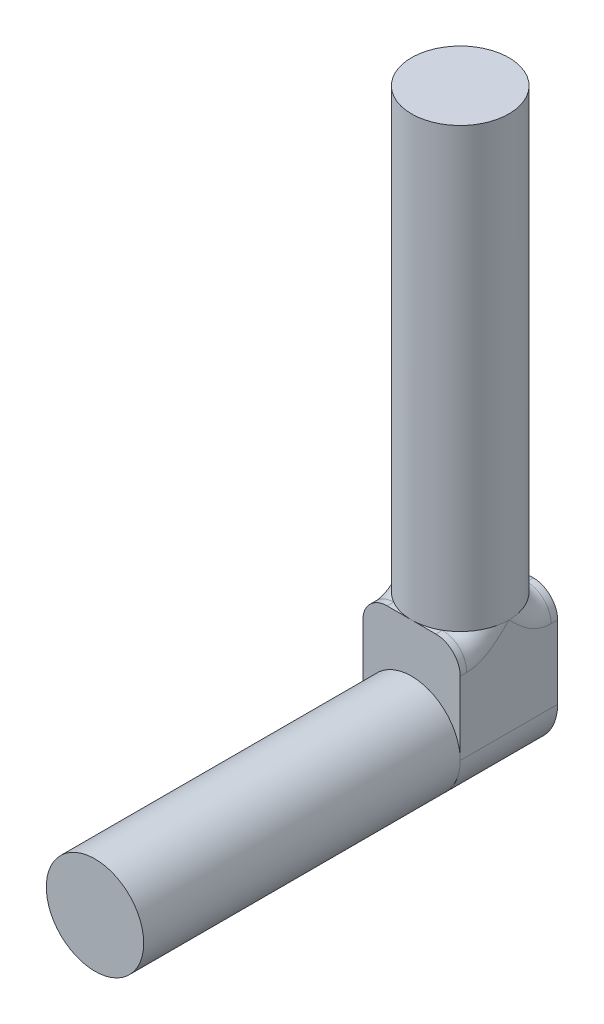
SolidWorks part; units mm, degrees
ref_plane "Front Plane" through (0, 0, 0) normal (0, 0, 1) x (1, 0, 0)
ref_plane "Top Plane" through (0, 0, 0) normal (0, 1, 0) x (1, 0, 0)
ref_plane "Right Plane" through (0, 0, 0) normal (1, 0, 0) x (0, 0, -1)
sketch "Sketch1" plane through (0, 0, 0) normal (0, 1, 0) x (1, 0, 0)
  circle A0 centre (0, 0) radius 2
  dimension "D1" = 4
extrude "Boss-Extrude1" add sketch "Sketch1" along normal blind 18
sketch "Sketch2" plane through (0, 0, 0) normal (0, -1, 0) x (1, 0, 0)
  line L1 (-2, -2) -> (2, -2)
  line L2 (-2, -2) -> (-2, 2)
  line L3 (-2, 2) -> (2, 2)
  line L4 (2, -2) -> (2, 2)
  line L5 (-2, -2) -> (2, 2) construction
  line L6 (-2, 2) -> (2, -2) construction
  point P0 (0, 0)
  dimension "D1" = 4
  dimension "D2" = 4
extrude "Boss-Extrude2" add sketch "Sketch2" along normal blind 6
sketch "Sketch3" plane through (0, 0, 2) normal (0, 0, 1) x (1, 0, 0)
  circle A0 centre (0, -3.9981) radius 2
  dimension "D1" = 4
extrude "Boss-Extrude3" add sketch "Sketch3" along normal blind 13
fillet "Fillet1" radius 1 4 edges at (2, 0, -1) (-2, 0, -1) (2, 0, 1) (-2, 0, 1)
fillet "Fillet2" radius 2 2 edges at (-2, -6, 0) (2, -6, 0)
sketch "Sketch4" plane through (0, 0, 15) normal (0, 0, 1) x (1, 0, 0)
  point P0 (0, -3.9981)
